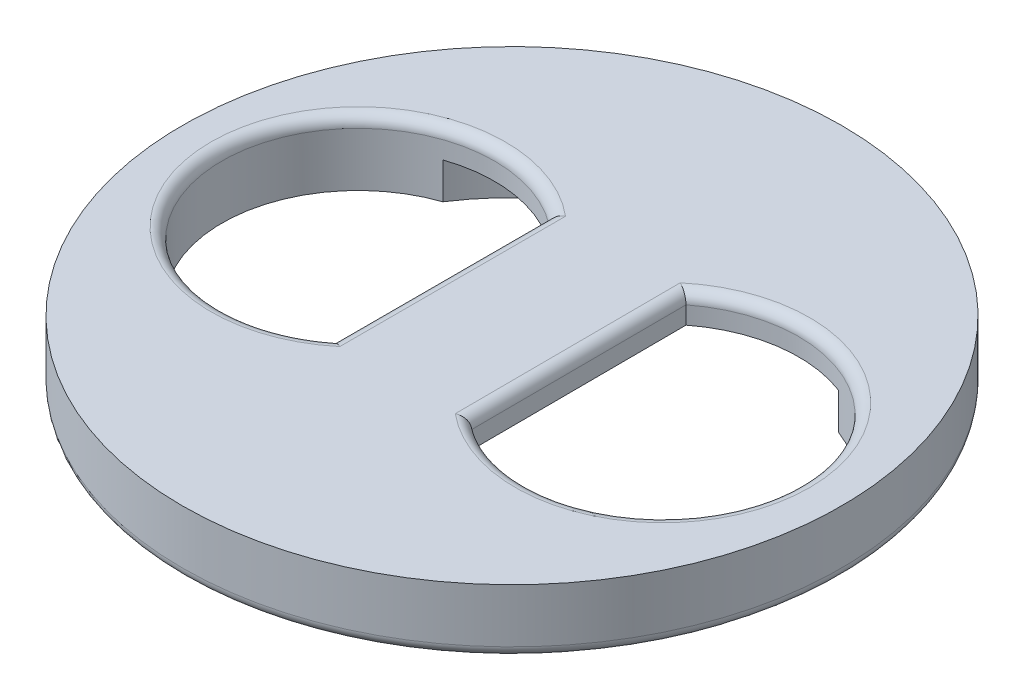
SolidWorks part; units mm, degrees
note: The reader was unsure of these and kept them because the rebuilt part matched: shared geometry of "Sketch1<3>", "Sketch1<5>".
ref_plane "Front Plane" through (0, 0, 0) normal (0, 0, 1) x (1, 0, 0)
ref_plane "Top Plane" through (0, 0, 0) normal (0, 1, 0) x (1, 0, 0)
ref_plane "Right Plane" through (0, 0, 0) normal (1, 0, 0) x (0, 0, -1)
sketch "Sketch1" plane through (0, 0, 0) normal (0, 1, 0) x (1, 0, 0)
  line L0 (0, 0) -> (-15, 0) construction
  line L1 (-3.2, 4.899) -> (-3.2, -4.899)
  line L2 (3.0343, 4.8844) -> (3.0718, -4.9135)
  circle A0 centre (0, 0) radius 15
  circle A2 centre (-7, 0) radius 6.2
  circle A3 centre (0, 0) radius 10.75
  circle A4 centre (6.853, 0) radius 6.2
  dimension "D1" = 30
  dimension "D2" = 8
  dimension "D3" = 12.4
  dimension "D4" = 21.5
  dimension "D5" = 12.4
  dimension "D6" = 3.8
  dimension "D7" = 3.8
extrude "Boss-Extrude1" add sketch "Sketch1" along normal blind 1.3
extrude "Boss-Extrude2" add sketch "Sketch1<3>" against normal blind 1.65 contours A0 | A3
sketch "Sketch1<3>" plane through (0, 0, 0) normal (0, 1, 0) x (1, 0, 0) same geometry as "Sketch1"
extrude "Cut-Extrude1" cut sketch "Sketch1<5>" against normal blind 10 contours L0 A3 A2 | A3 L0 A2 | A3 A4
sketch "Sketch1<5>" plane through (0, 0, 0) normal (0, 1, 0) x (1, 0, 0) same geometry as "Sketch1"
fillet "Fillet5" radius 0.5 4 edges at (-13.2, 1.3, 0) (13.053, 1.3, -0.0238) (3.0531, 1.3, 0.0145) (-3.2, 1.3, 0)
fillet "Fillet6" radius 0.5 2 edges at (0.0412, -1.65, 10.7499) (0, -1.65, 15)
